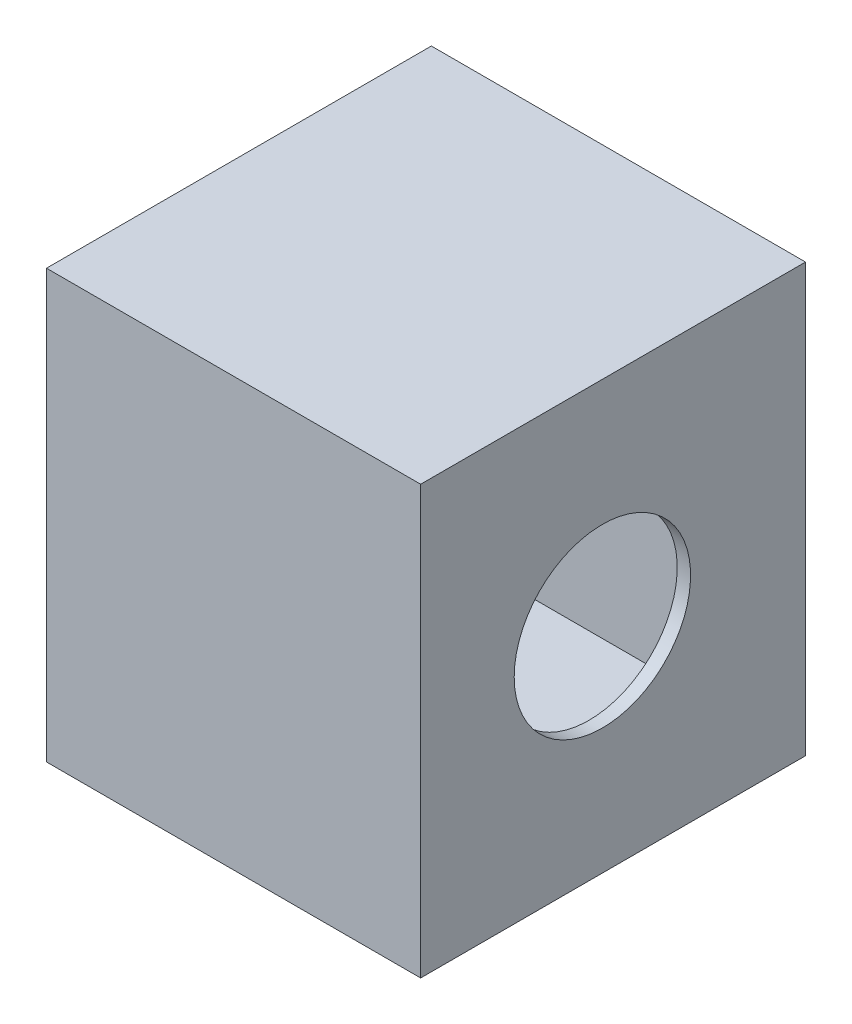
SolidWorks part; units mm, degrees
ref_plane "Front Plane" through (0, 0, 0) normal (0, 0, 1) x (1, 0, 0)
ref_plane "Top Plane" through (0, 0, 0) normal (0, 1, 0) x (1, 0, 0)
ref_plane "Right Plane" through (0, 0, 0) normal (1, 0, 0) x (0, 0, -1)
sketch "S_box1" plane through (0, 0, 0) normal (0, 0, 1) x (1, 0, 0)
  line L0 (-35, -40) -> (35, -40)
  line L1 (35, -40) -> (35, 40)
  line L2 (35, 40) -> (-35, 40)
  line L3 (-35, 40) -> (-35, -40)
  dimension "P1" = 35
  dimension "P2" = 40
  dimension "P3" = 35
  dimension "P4" = 40
  dimension "P5" = 35
  dimension "P6" = 40
  dimension "P7" = 35
  dimension "P8" = 40
extrude "Boss_1" add sketch "S_box1" along normal blind 72
ref_plane "PZ_p2_500" through (0, 0, 2.5) normal (0, 0, 1) x (1, 0, 0)
sketch "S_cut2" plane through (0, 0, 2.5) normal (0, 0, 1) x (1, 0, 0)
  line L0 (-36, -37.5) -> (32.5, -37.5)
  line L1 (32.5, -37.5) -> (32.5, 37.5)
  line L2 (32.5, 37.5) -> (-36, 37.5)
  line L3 (-36, 37.5) -> (-36, -37.5)
  dimension "P1" = 36
  dimension "P2" = 37.5
  dimension "P3" = 32.5
  dimension "P4" = 37.5
  dimension "P5" = 32.5
  dimension "P6" = 37.5
  dimension "P7" = 36
  dimension "P8" = 37.5
extrude "Pocket_2" cut sketch "S_cut2" along normal blind 67
ref_plane "PX_p32_400" through (32.4, 0, 0) normal (1, 0, 0) x (0, 0, -1)
sketch "S_hole3" plane through (32.4, 0, 0) normal (1, 0, 0) x (0, 0, -1)
  circle A0 centre (-38, 0) radius 16.5
  dimension "D1_S_hole3" = 33
  dimension "P2" = 38
extrude "Hole_3" cut sketch "S_hole3" along normal blind 2.7
ref_plane "PZ_m0_100" through (0, 0, -0.1) normal (0, 0, 1) x (1, 0, 0)
sketch "S_hole4" plane through (0, 0, -0.1) normal (0, 0, 1) x (1, 0, 0)
  circle A0 centre (0, 0) radius 1.5
  dimension "D1_S_hole4" = 3
extrude "Hole_4" cut sketch "S_hole4" along normal blind 2.7
sketch "S_hole5" plane through (0, 0, -0.1) normal (0, 0, 1) x (1, 0, 0)
  circle A0 centre (0, 7) radius 0.8
  dimension "D1_S_hole5" = 1.6
  dimension "P2" = 7
extrude "Hole_5" cut sketch "S_hole5" along normal blind 2.7
sketch "S_hole6" plane through (0, 0, -0.1) normal (0, 0, 1) x (1, 0, 0)
  circle A0 centre (0, -7) radius 0.8
  dimension "D1_S_hole6" = 1.6
  dimension "P2" = 7
extrude "Hole_6" cut sketch "S_hole6" along normal blind 2.7
equation "\"plate_t\" = 3"
equation "\"clearance\" = 0.4"
